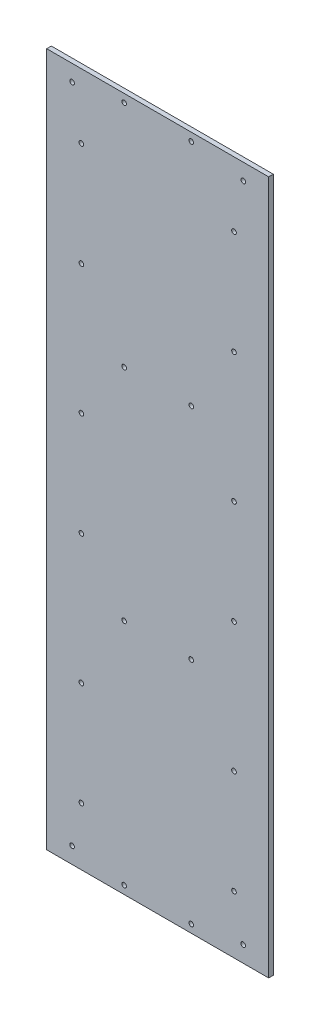
SolidWorks part; units mm, degrees
material "Alumina"
ref_plane "Front Plane" through (0, 0, 0) normal (0, 0, 1) x (1, 0, 0)
ref_plane "Top Plane" through (0, 0, 0) normal (0, 1, 0) x (1, 0, 0)
ref_plane "Right Plane" through (0, 0, 0) normal (1, 0, 0) x (0, 0, -1)
sketch "Sketch1" plane through (0, 0, 0) normal (0, 0, 1) x (1, 0, 0)
  line L1 (48, -150) -> (-48, -150)
  line L2 (48, -150) -> (48, 150)
  line L3 (48, 150) -> (-48, 150)
  line L4 (-48, -150) -> (-48, 150)
  line L5 (48, -150) -> (-48, 150) construction
  line L6 (48, 150) -> (-48, -150) construction
  point P0 (0, 0)
  dimension "D1" = 96
  dimension "D2" = 300
extrude "Boss-Extrude1" add sketch "Sketch1" along normal blind 2
sketch "Sketch2" plane through (0, 0, 2) normal (0, 0, 1) x (1, 0, 0)
  line L0 (-48, 150) -> (-48, -150) construction
  line L1 (48, 150) -> (-48, 150) construction
  line L2 (-48, -150) -> (48, -150) construction
  line L3 (48, -150) -> (48, 150) construction
  line L4 (0, -1.1) -> (0, 1.1) construction
  line L5 (-33, 77) -> (-33, -125) construction
  line L6 (33, 77) -> (33, -125) construction
  line L7 (-14.5, 146.5) -> (14.5, 146.5) construction
  line L8 (14.5, 146.5) -> (14.5, -146.5) construction
  line L9 (14.5, -146.5) -> (-14.5, -146.5) construction
  line L10 (-14.5, -146.5) -> (-14.5, 146.5) construction
  circle A0 centre (-33, 122) radius 1
  circle A1 centre (-33, 77) radius 1
  circle A9 centre (-33, -125) radius 1
  circle A13 centre (14.5, -146.5) radius 1
  circle A14 centre (-14.5, -146.5) radius 1
  circle A15 centre (-14.5, -47.5) radius 1
  circle A17 centre (-14.5, 47.5) radius 1
  circle A19 centre (-14.5, 146.5) radius 1
  circle A20 centre (14.5, 146.5) radius 1
  circle A21 centre (-33, -80) radius 1
  circle A22 centre (-33, -24) radius 1
  circle A23 centre (-33, 21) radius 1
  circle A24 centre (33, 21) radius 1
  circle A25 centre (33, -24) radius 1
  circle A26 centre (33, -80) radius 1
  circle A27 centre (33, -125) radius 1
  circle A28 centre (33, 77) radius 1
  circle A29 centre (33, 122) radius 1
  circle A30 centre (14.5, -47.5) radius 1
  circle A31 centre (14.5, 47.5) radius 1
  point P31 (-14.5, -51.3049)
  point P34 (-14.5, 47.5)
  dimension "D1" = 2
  dimension "D3" = 28
  dimension "D4" = 2
  dimension "D6" = 15
  dimension "D10" = 2
  dimension "D11" = 33.5
  dimension "D13" = 3.5
  dimension "D15" = 2
  dimension "D8" = 2
  dimension "D14" = 2
  dimension "D17" = 45
  dimension "D18" = 56
  dimension "D19" = 2
  dimension "D20" = 45
  dimension "D12" = 2
  dimension "D21" = 2
  dimension "D23" = 2
  dimension "D24" = 99
  dimension "D25" = 2
  dimension "D2" = 15
  dimension "D5" = 45
  dimension "D9" = 25
  dimension "D16" = 3.5
  dimension "D7" = 15
  dimension "D22" = 99
extrude "Cut-Extrude1" cut sketch "Sketch2" against normal blind 10
sketch "Sketch3" plane through (0, 0, 2) normal (0, 0, 1) x (1, 0, 0)
  line L0 (-37, 143) -> (37, 143) construction
  line L1 (37, 143) -> (37, -143) construction
  line L2 (37, -143) -> (-37, -143) construction
  line L3 (-37, -143) -> (-37, 143) construction
  line L4 (-48, 150) -> (-48, -150) construction
  line L5 (48, -150) -> (48, 150) construction
  line L6 (48, 150) -> (-48, 150) construction
  line L7 (-48, -150) -> (48, -150) construction
  circle A0 centre (-37, 143) radius 1
  circle A1 centre (37, 143) radius 1
  circle A2 centre (-37, -143) radius 1
  circle A3 centre (37, -143) radius 1
  dimension "D5" = 2
  dimension "D6" = 2
  dimension "D7" = 2
  dimension "D8" = 2
  dimension "D1" = 11
  dimension "D2" = 11
  dimension "D3" = 7
  dimension "D4" = 7
extrude "Cut-Extrude2" cut sketch "Sketch3" against normal blind 10
